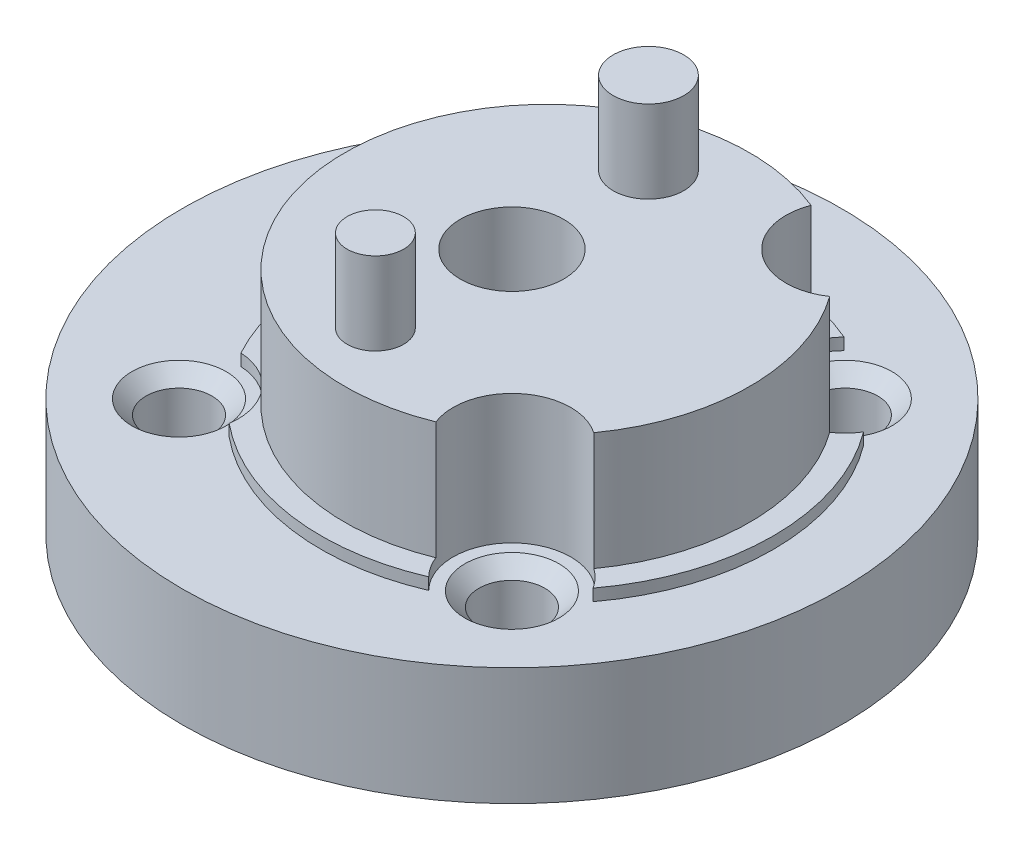
SolidWorks part; units mm, degrees
ref_plane "Front Plane" through (0, 0, 0) normal (0, 0, 1) x (1, 0, 0)
ref_plane "Top Plane" through (0, 0, 0) normal (0, 1, 0) x (1, 0, 0)
ref_plane "Right Plane" through (0, 0, 0) normal (1, 0, 0) x (0, 0, -1)
sketch "Sketch1" plane through (0, 0, 0) normal (0, 1, 0) x (1, 0, 0)
  circle A0 centre (0, 0) radius 14
  dimension "D1" = 28
extrude "Boss-Extrude1" add sketch "Sketch1" along normal blind 5
sketch "Sketch2" plane through (0, 5, 0) normal (0, 1, 0) x (1, 0, 0)
  line L0 (-7.7, 0) -> (7.7, 0) construction
  circle A0 centre (1.5, 0) radius 9.6
  dimension "D1" = 19.2
  dimension "D2" = 1.5
extrude "Boss-Extrude2" add sketch "Sketch2" along normal blind 0.5
sketch "Sketch3" plane through (0, 5.5, 0) normal (0, 1, 0) x (1, 0, 0)
  circle A0 centre (1.5, 0) radius 8.6
  dimension "D1" = 17.2
extrude "Boss-Extrude3" add sketch "Sketch3" along normal blind 5
sketch "Sketch4" plane through (0, 5, 0) normal (0, 1, 0) x (1, 0, 0)
  line L0 (-0.1258, 0) -> (-17.3037, 0) construction
  line L1 (-3.025, 0) -> (3.025, 0) construction
  line L2 (0, 0) -> (-7.0711, 7.0711) construction
  circle A0 centre (-7.0711, 7.0711) radius 1.4
  dimension "D1" = 2.8
  dimension "D2" = 45
  dimension "D3" = 10
extrude "Cut-Extrude1" cut sketch "Sketch4" against normal through all
pattern_circular "CirPattern1" count 4 over 360 about axis through (0, 5, 0) along (0, -1, 0) of "Cut-Extrude1"
sketch "Sketch5" plane through (0, 5, 0) normal (0, 1, 0) x (1, 0, 0)
  circle A0 centre (-7.0711, 7.0711) radius 2.5
  circle A1 centre (7.0711, 7.0711) radius 2.5
  circle A2 centre (7.0711, -7.0711) radius 2.5
  circle A3 centre (-7.0711, -7.0711) radius 2.5
  point P12 (0, 0)
  dimension "D1" = 5
extrude "Cut-Extrude2" cut sketch "Sketch5" along normal through all
chamfer "Chamfer1" distance 0.6 angle 45 4 edges at (-5.6711, 5, 7.0711) (7.0711, 5, 5.6711) (5.6711, 5, -7.0711) (-7.0711, 5, -5.6711)
sketch "Sketch6" plane through (0, 0, 0) normal (0, -1, 0) x (1, 0, 0)
  circle A0 centre (0, 0) radius 4.35
  dimension "D1" = 8.7
extrude "Cut-Extrude3" cut sketch "Sketch6" against normal blind 2.5
sketch "Sketch7" plane through (0, 10.5, 0) normal (0, 1, 0) x (1, 0, 0)
  circle A0 centre (0, 0) radius 2.2
  dimension "D1" = 4.4
extrude "Cut-Extrude4" cut sketch "Sketch7" against normal blind 6.5
sketch "Sketch8" plane through (0, 10.5, 0) normal (0, 1, 0) x (1, 0, 0)
  line L0 (0, -3.025) -> (0, 3.025) construction
  circle A0 centre (0, 5.8) radius 1.5
  circle A2 centre (0, -5.8) radius 1.2
  dimension "D1" = 3
  dimension "D4" = 2.4
  dimension "D2" = 5.8
  dimension "D3" = 5.8
extrude "Boss-Extrude4" add sketch "Sketch8" along normal blind 3.5
equation "\"pin_circle_R\" = 27"
equation "\"ecc\" = 1.5"
equation "\"n_pins\" = 11"
equation "\"pin_d\" = 3"
equation "\"out_pin_R\" = 18.5"
equation "\"disc_clr\" = 0.1"
equation "\"seat_6803\" = 26.1"
equation "\"disc_t\" = 5"
equation "\"out_hole_clr\" = 0.5"
equation "\"boss_17\" = 17.20"
equation "\"rotor_bolt_R\" = 10"
equation "\"m25_clr\" = 2.8"
equation "\"m25_head\" = 5"
equation "\"insert_hole\" = 4.4"
equation "\"D2@Sketch2\"=\"ecc\""
equation "\"D1@Sketch3\"=\"boss_17\""
equation "\"D1@Sketch4\"=\"m25_clr\""
equation "\"D3@Sketch4\"=\"rotor_bolt_R\""
equation "\"csk\" = 0.6"
equation "\"peg_d\" = 3.0"
equation "\"D1@Sketch5\"=\"m25_head\""
equation "\"D1@Chamfer1\"=\"csk\""
equation "\"D1@Sketch7\"=\"insert_hole\""
equation "\"D1@Sketch8\"=\"peg_d\""
equation "\"D4@Sketch8\"=\"peg_d\" - 0.6"
equation "\"seat_6806\" = 42.1"
equation "\"plug_d\" = 8.6"
equation "\"peg_clr\" = 0.3"
equation "\"m3_clr\" = 3.4"
equation "\"m3_head\" = 6.2"
equation "\"pin_press\" = 3.2"
equation "\"pin_slip\" = 3.3"
equation "\"hub_30\" = 30.25"
equation "\"hub_short\" = 0.2"
equation "\"m3_tap\" = 2.8"
equation "\"D1@Sketch6\"=\"plug_d\" + 0.1"
equation "\"rear_plate_t\" = 2"
equation "\"motor_ring\" = 40.4"
